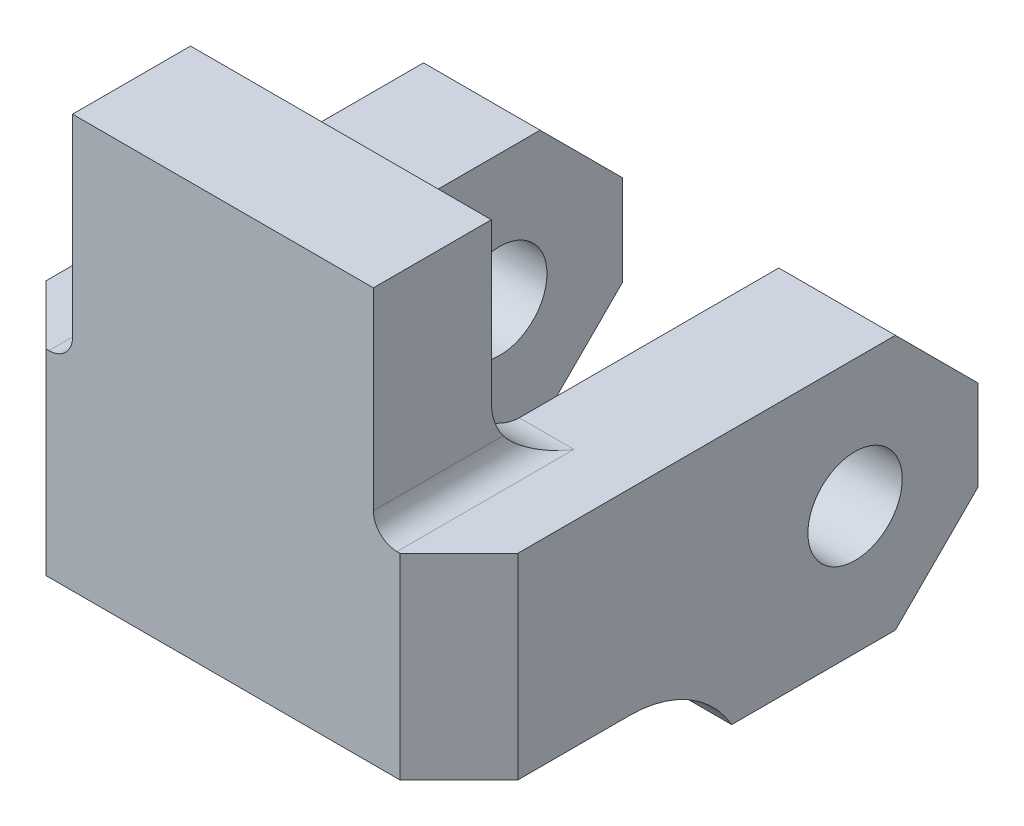
SolidWorks part; units mm, degrees
ref_plane "Спереди" through (0, 0, 0) normal (0, 0, 1) x (1, 0, 0)
ref_plane "Сверху" through (0, 0, 0) normal (0, 1, 0) x (1, 0, 0)
ref_plane "Справа" through (0, 0, 0) normal (1, 0, 0) x (0, 0, -1)
sketch "Эскиз1" plane through (0, 0, 0) normal (0, 1, 0) x (1, 0, 0)
  line L1 (-12.75, -17.1196) -> (12.75, -17.1196)
  line L2 (-12.75, -17.1196) -> (-12.75, -27.1196)
  line L3 (-12.75, -27.1196) -> (12.75, -27.1196)
  line L4 (12.75, -17.1196) -> (12.75, -27.1196)
  point P0 (0, 0)
extrude "Вытянуть1" add sketch "Эскиз1" along normal blind 40
sketch "Эскиз2" plane through (0, 0, 27.1196) normal (0, 0, -1) x (-1, 0, 0)
  line L1 (-2.9899, 0) -> (-13.5417, 0) construction
  line L2 (-20, 21.641) -> (20, 21.641)
  line L3 (-20, 21.641) -> (-20, 0)
  line L4 (-20, 0) -> (20, 0)
  line L5 (0, 40) -> (0, 26.8323) construction
  line L7 (20, 21.641) -> (20, 0)
  line L8 (-20, 21.641) -> (20, 0) construction
  line L9 (-20, 0) -> (20, 21.641) construction
  point P0 (0, 10.8205)
extrude "Вытянуть2" add sketch "Эскиз2" along normal blind 44
sketch "Эскиз3" plane through (0, 27.1196, 17.1196) normal (0, 0, -1) x (1, 0, 0)
  line L0 (0, -14.8804) -> (0, -53.0274) construction
  line L2 (20, 27.1196) -> (-20, 27.1196) construction
  line L3 (10.1144, 54.8564) -> (-10.1144, 54.8564)
  line L4 (10.1144, 54.8564) -> (10.1144, -0.6172)
  line L5 (10.1144, -0.6172) -> (-10.1144, -0.6172)
  line L6 (-10.1144, 54.8564) -> (-10.1144, -0.6172)
  line L7 (10.1144, 54.8564) -> (-10.1144, -0.6172) construction
  line L8 (10.1144, -0.6172) -> (-10.1144, 54.8564) construction
  point P1 (0, 27.1196)
extrude "Вытянуть3" cut sketch "Эскиз3" along normal through all
fillet "Скругление2" radius 5 2 edges at (-11.4322, 21.641, 17.1196) (11.4322, 21.641, 17.1196)
fillet "Скругление3" radius 2 2 edges at (-12.75, 21.641, 19.6196) (12.75, 21.641, 19.6196)
chamfer "Фаска1" distance 7 angle 45 4 edges at (-15.0572, 0, -16.8804) (15.0572, 0, -16.8804) (-15.0572, 21.641, -16.8804) (15.0572, 21.641, -16.8804)
sketch "Эскиз4" plane through (20, 0, 0) normal (1, 0, 0) x (0, 0, -1)
  circle A0 centre (6.461, 10.8205) radius 4
extrude "Вырез-Вытянуть1" cut sketch "Эскиз4" against normal through all
fillet "Скругление4" radius 5 2 edges at (-10.1144, 13.3205, 17.1196) (10.1144, 13.3205, 17.1196)
chamfer "Фаска2" distance 5 angle 45 2 edges at (-20, 10.8205, 27.1196) (20, 10.8205, 27.1196)
sketch "Эскиз5" plane through (0, 0, 0) normal (0, -1, 0) x (1, 0, 0)
  line L1 (-23.9923, 28.7282) -> (22.9299, 28.7282)
  line L2 (-23.9923, 28.7282) -> (-23.9923, 3.9982)
  line L3 (-23.9923, 3.9982) -> (22.9299, 3.9982)
  line L4 (22.9299, 28.7282) -> (22.9299, 3.9982)
extrude "Вытянуть4" cut sketch "Эскиз5" against normal blind 5
fillet "Скругление5" radius 10 2 edges at (15.0572, 5, 3.9982) (-15.0572, 5, 3.9982)
